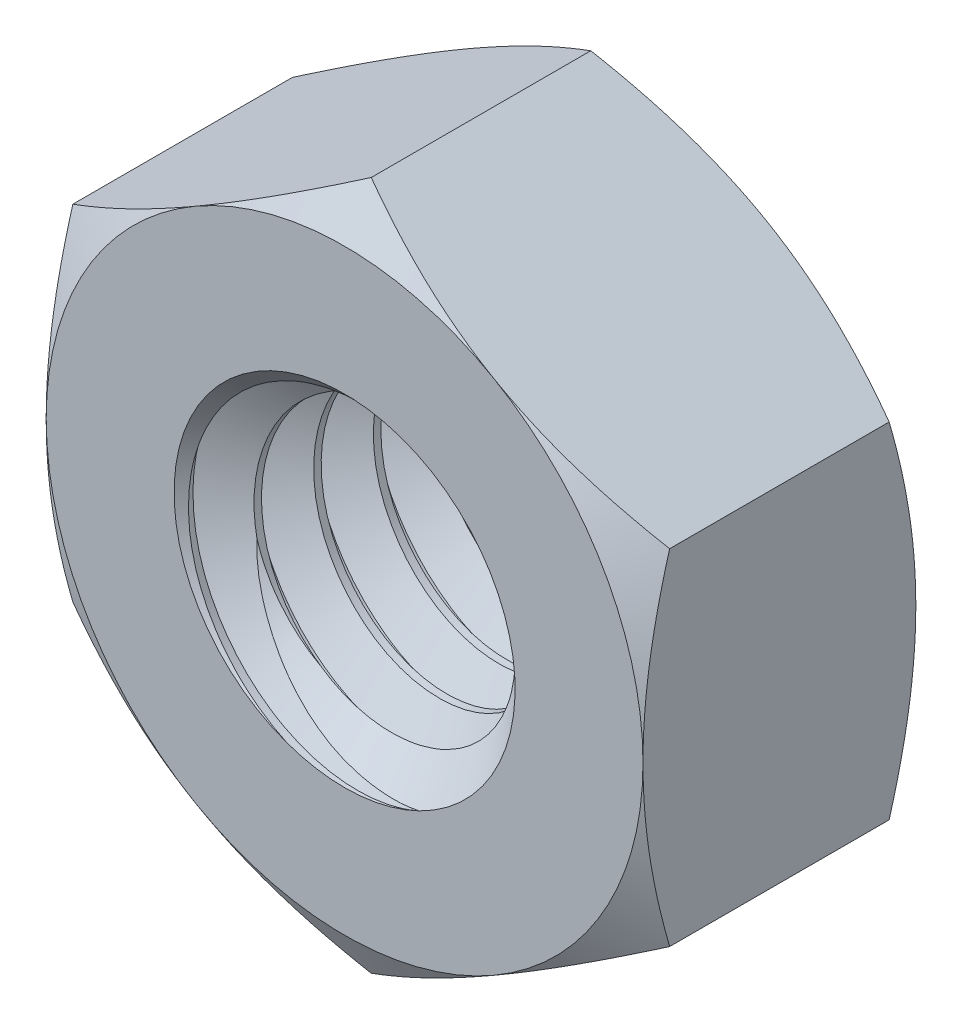
SolidWorks part; units mm, degrees
ref_plane "Front" through (0, 0, 0) normal (0, 0, 1) x (1, 0, 0)
ref_plane "Top" through (0, 0, 0) normal (0, 1, 0) x (1, 0, 0)
ref_plane "Right" through (0, 0, 0) normal (1, 0, 0) x (0, 0, -1)
sketch "Sketch1" plane through (0, 0, 0) normal (0, 0, 1) x (1, 0, 0)
  line L1 (-3.5, 2.0207) -> (-3.5, -2.0207)
  line L2 (-3.5, -2.0207) -> (0, -4.0415)
  line L3 (0, -4.0415) -> (3.5, -2.0207)
  line L4 (3.5, -2.0207) -> (3.5, 2.0207)
  line L5 (3.5, 2.0207) -> (0, 4.0415)
  line L6 (0, 4.0415) -> (-3.5, 2.0207)
  circle A0 centre (0, 0) radius 3.5 construction
  circle A1 centre (0, 0) radius 2 construction
  point P10 (0, 2)
  dimension "hex" = 7
  dimension "dia" = 4
extrude "Extrude1" add sketch "Sketch1" along normal mid plane 3.2
sketch "Sketch4" plane through (0, 0, -1.6) normal (0, 0, -1) x (-1, 0, 0)
  circle A0 centre (0, 0) radius 2 construction
  circle A1 centre (0, 0) radius 2
sketch "Sketch10" plane through (0, 0, 1.6) normal (0, 0, 1) x (1, 0, 0)
  circle A0 centre (0, 0) radius 2 construction
  circle A1 centre (0, 0) radius 2
extrude "Cut-Extrude2" cut sketch "Sketch10" against normal through all draft 45
sketch "Sketch11" plane through (0, 0, -1.6) normal (0, 0, -1) x (-1, 0, 0)
  circle A0 centre (0, 0) radius 2 construction
  circle A1 centre (0, 0) radius 2
extrude "Cut-Extrude3" cut sketch "Sketch11" against normal through all draft 45
sketch "Sketch13" plane through (0, 0, -1.6) normal (0, 0, -1) x (-1, 0, 0)
  circle A0 centre (0, 0) radius 2 construction
  circle A1 centre (0, 0) radius 2
extrude "Boss-Extrude1" add sketch "Sketch13" against normal up to vertex (3.2 mm away) separate body up to point (-3.5, 2.0207, 1.6)
curve "Helix/Spiral3" pitch 0.7 height 3.2 radius 2 centre (0, 0, -1.6) axis (0, 0, 1) start towards (0, 1, 0)
sketch "Sketch12" plane through (0, 0, 0) normal (1, 0, 0) x (0, 0, -1)
  line L0 (2.2125, 2) -> (1.6, 2)
  line L1 (2.2125, 2) -> (1.95, 1.5453)
  line L2 (1.95, 1.5453) -> (1.8625, 1.5453)
  line L3 (1.8625, 1.5453) -> (1.6, 2)
  line L4 (1.9062, 1.5453) -> (1.9062, 2) construction
  line L5 (1.7312, 1.7727) -> (2.0812, 1.7727) construction
  dimension "D1" = 60
  dimension "D2" = 0.0875
  dimension "D3" = 0.35
sweep "Cut-Sweep1" cut profiles "Sketch12" path "Helix/Spiral3" align with end faces yes
combine bodies "Combine1" operation type subtract main body 116 bodies to subtract 118
sketch "Sketch7" plane through (0, 0, 1.6) normal (0, 0, 1) x (1, 0, 0)
  circle A0 centre (0, 0) radius 3.5 construction
  circle A1 centre (0, 0) radius 3.5
extrude "Extrude2" cut sketch "Sketch7" against normal blind 25.4 draft 60 flip side to cut
mirror "Mirror2" about plane through (0, 0, 0) normal (0, 0, 1) of "Extrude2"
sketch "Sketch8" plane through (0, 0, 1.6) normal (0, 0, 1) x (1, 0, 0)
  line L0 (-1.4142, 1.4142) -> (0, 0) construction
  line L1 (0, -2.0692) -> (0, 2.0692) construction
  circle A1 centre (0, 0) radius 2 construction
  point P0 (-1.4142, 1.4142)
  dimension "D1" = 45
sketch "Sketch14" plane through (0, 0, 1.6) normal (0, 0, 1) x (1, 0, 0)
  line L0 (0, 0) -> (-2, 0) construction
  arc A0 (-0.6746, -1.8828) -> (0.8737, -1.7991) centre (0, 0) ccw construction
equation "\"D3@Helix/Spiral3\" = \"length@Extrude1\" "
equation "\"D2@Sketch12\" = \"D4@Helix/Spiral3\"*.125"
equation "\"D3@Sketch12\" = \"D4@Helix/Spiral3\"*.50"
